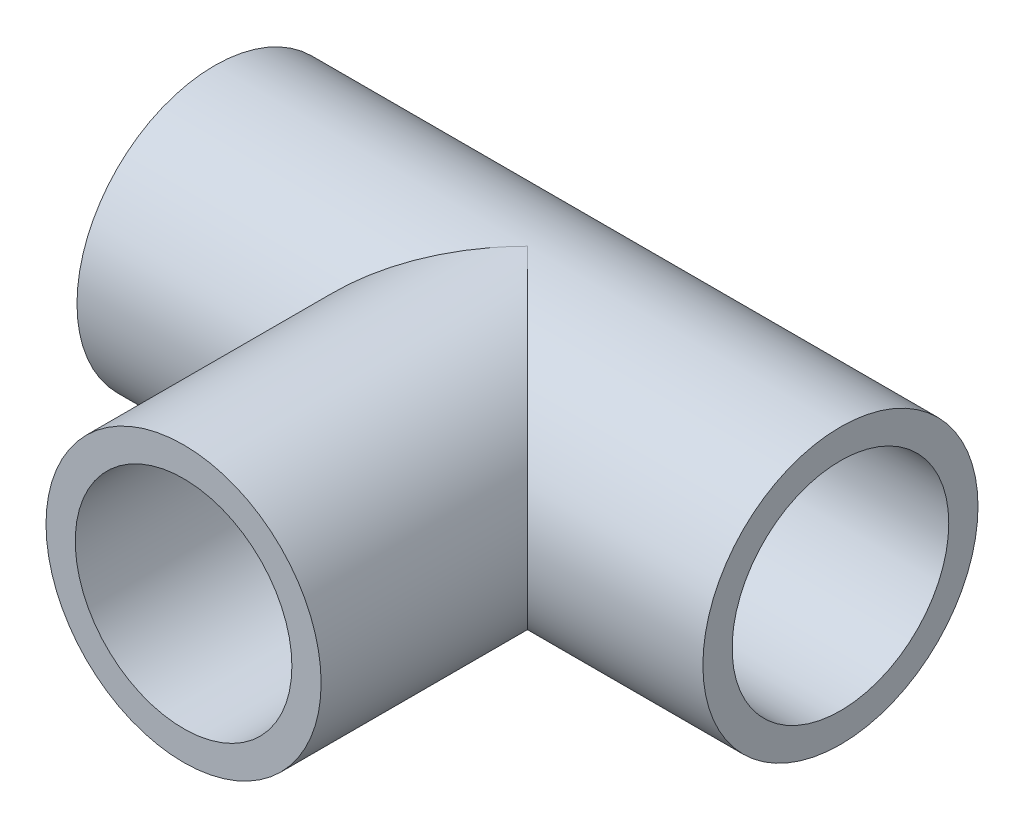
SolidWorks part; units mm, degrees
ref_plane "Front Plane" through (0, 0, 0) normal (0, 0, 1) x (1, 0, 0)
ref_plane "Top Plane" through (0, 0, 0) normal (0, 1, 0) x (1, 0, 0)
ref_plane "Right Plane" through (0, 0, 0) normal (1, 0, 0) x (0, 0, -1)
sketch "Sketch1" plane through (0, 0, 0) normal (1, 0, 0) x (0, 0, -1)
  circle A0 centre (0, 0) radius 6.35
  circle A1 centre (0, 0) radius 10.16
extrude "Boss-Extrude2" add sketch "Sketch1" along normal blind 20.828
sketch "Sketch2" plane through (0, 0, 0) normal (-1, 0, 0) x (0, 0, 1)
  circle A0 centre (0, 0) radius 8.001
  circle A1 centre (0, 0) radius 10.16
sketch "Sketch3" plane through (20.828, 0, 0) normal (1, 0, 0) x (0, 0, -1)
  circle A0 centre (0, 0) radius 8.001
  circle A1 centre (0, 0) radius 10.16
sketch "Sketch8" plane through (0, 0, 0) normal (0, 0, 1) x (1, 0, 0)
  circle A0 centre (10.4106, 0) radius 10.16
  circle A1 centre (10.4106, 0) radius 6.35
extrude "Boss-Extrude5" add sketch "Sketch8" along normal blind 12.7
extrude "Boss-Extrude6" add sketch "Sketch2" along normal blind 12.7
extrude "Boss-Extrude7" add sketch "Sketch3" along normal blind 12.7
sketch "Sketch9" plane through (0, 0, 12.7) normal (0, 0, 1) x (1, 0, 0)
  circle A0 centre (10.4106, 0) radius 8.001
  circle A1 centre (10.4106, 0) radius 10.16
extrude "Boss-Extrude8" add sketch "Sketch9" along normal blind 12.7
sketch "Sketch10" plane through (0, 0, 0) normal (0, 0, 1) x (1, 0, 0)
  circle A0 centre (10.4106, 0) radius 6.281
extrude "Cut-Extrude1" cut sketch "Sketch10" against normal blind 0.0001 and the other way blind 15.24
sketch "Sketch11" plane through (0, 0, 0) normal (1, 0, 0) x (0, 0, -1)
  circle A0 centre (0, 0) radius 6.35
extrude "Cut-Extrude2" cut sketch "Sketch11" against normal blind 0.0001 and the other way blind 25.4
